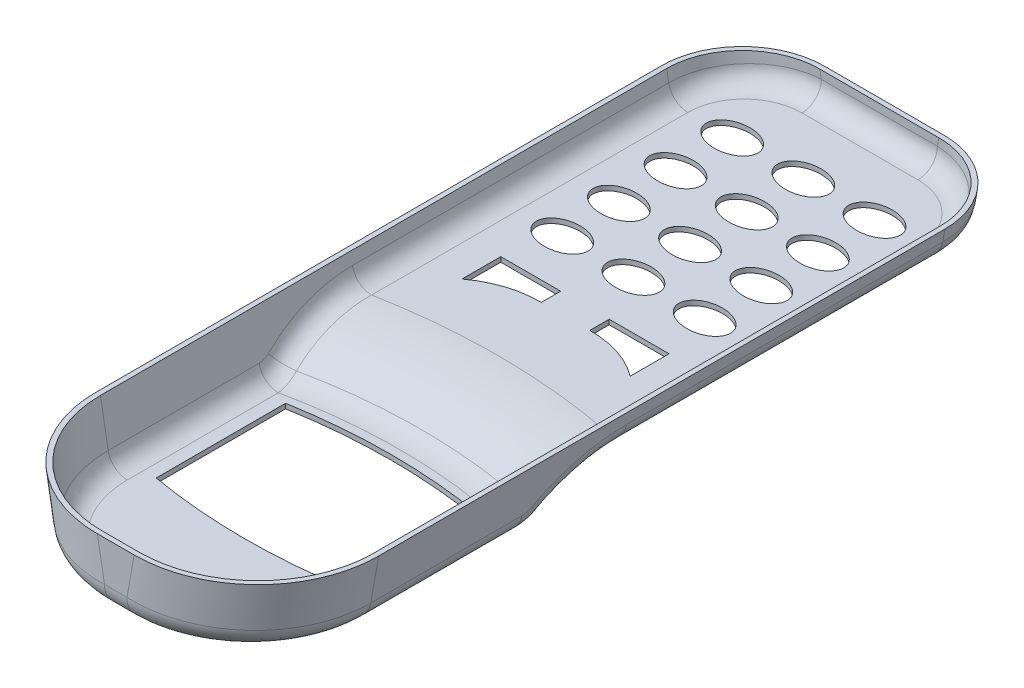
SolidWorks part; units mm, degrees
ref_plane "정면" through (0, 0, 0) normal (0, 0, 1) x (1, 0, 0)
ref_plane "윗면" through (0, 0, 0) normal (0, 1, 0) x (1, 0, 0)
ref_plane "우측면" through (0, 0, 0) normal (1, 0, 0) x (0, 0, -1)
sketch "스케치1" plane through (0, 0, 0) normal (0, 1, 0) x (1, 0, 0)
  line L1 (-8.75, 47.5) -> (8.75, 47.5)
  line L2 (-8.75, 47.5) -> (-8.75, 0)
  line L3 (-8.75, 0) -> (8.75, 0)
  line L4 (8.75, 47.5) -> (8.75, 0)
  dimension "D1" = 17.5
  dimension "D2" = 47.5
extrude "보스-돌출1" add sketch "스케치1" along normal blind 2
sketch "스케치2" plane through (0, 0, 0) normal (0, -1, 0) x (1, 0, 0)
  line L1 (-8.75, 0) -> (8.75, 0)
  line L2 (-8.75, 0) -> (-8.75, -18.8886)
  line L4 (8.75, 0) -> (8.75, -18.8886)
  arc A0 (-8.75, -18.8886) -> (8.75, -18.8886) centre (0, 15) ccw
  point P10 (0, 0)
  dimension "D2" = 35
  dimension "D1" = 18.8886
extrude "보스-돌출2" add sketch "스케치2" along normal blind 2
sketch "스케치3" plane through (0, 0, -47.5) normal (0, 0, -1) x (-1, 0, 0)
  line L0 (-8.75, 2) -> (-8.0447, -2)
  line L2 (-8.0447, -2) -> (-8.75, -2)
  line L3 (-8.75, -2) -> (-8.75, 2)
  line L4 (-8.75, 2) -> (8.75, 2) construction
  line L5 (0, 9.4756) -> (0, -9.7155) construction
  line L6 (8.75, -2) -> (8.75, 2)
  line L7 (8.0447, -2) -> (8.75, -2)
  line L8 (8.75, 2) -> (8.0447, -2)
  line L9 (-8.75, -2) -> (8.75, -2) construction
  point P3 (-7.9664, -2.4442)
  point P15 (0, 0)
  dimension "D1" = 80
extrude "컷-돌출1" cut sketch "스케치3" against normal through all
fillet "필렛1" radius 7.5 2 edges at (8.3973, 0, 0) (-8.3973, 0, 0)
fillet "필렛2" radius 5 2 edges at (8.5737, 1, -47.5) (-8.5737, 1, -47.5)
fillet "필렛3" radius 2.5 1 edges at (0, -2, -20)
fillet "필렛4" radius 7.7 1 edges at (0, 0, -20)
fillet "필렛5" radius 1.5 14 edges at (0, -2, 0) (0, 0, -47.5) (5.8141, -2, -2.1967) (-5.8141, -2, -2.1967) (-8.0447, -2, -12.0204) (-8.3973, 0, -32.5964) (-6.9103, 0, -46.0355) (6.9103, 0, -46.0355) (8.3973, 0, -32.5964) (8.0447, -2, -12.0204) (-8.0795, -1.8026, -17.5361) (8.0689, -1.8624, -17.3781) (-8.3226, -0.4242, -20.1239) (8.3349, -0.3539, -20.3395)
shell "쉘1" thickness 0.3 removed face at (0, 2, -24.2456)
sketch "스케치4" plane through (0, -2, 0) normal (0, -1, 0) x (1, 0, 0)
  line L2 (-6, -8.5) -> (-6, -16.5)
  line L4 (6, -8.5) -> (6, -16.5)
  arc A0 (-6, -8.5) -> (6, -8.5) centre (0, -42.9819) cw
  arc A1 (-6, -16.5) -> (6, -16.5) centre (0, 17.9819) ccw
  point P7 (0, 0)
  point P8 (0, 0)
  point P9 (0, 0)
  point P10 (0, 0)
  point P11 (0, 0)
  dimension "D5" = 35
  dimension "D6" = 35
  dimension "D1" = 8
  dimension "D2" = 12
  dimension "D3" = 8
  dimension "D4" = 6
  dimension "D7" = 8.5
extrude "컷-돌출2" cut sketch "스케치4" against normal through all
sketch "스케치5" plane through (0, 0, 0) normal (0, -1, 0) x (1, 0, 0)
  line L0 (3.5847, -47.5) -> (-3.5847, -47.5) construction
  line L1 (-16.3118, -42.5) -> (22.2927, -42.5) construction
  line L2 (-16.3118, -39) -> (22.2927, -39) construction
  line L3 (-16.3118, -35.5) -> (22.2927, -35.5) construction
  line L4 (-16.3118, -32) -> (22.2927, -32) construction
  line L5 (-5.2, -26.6) -> (-5.2, -29)
  line L6 (-5.2, -29) -> (-1.5, -29)
  line L7 (-1.5, -29) -> (-1.5, -27.8)
  line L8 (0, 0) -> (0, -65.6566) construction
  line L9 (1.5, -29) -> (1.5, -27.8)
  line L10 (5.2, -29) -> (1.5, -29)
  line L11 (5.2, -26.6) -> (5.2, -29)
  arc A0 (-5.2, -26.6) -> (-1.5, -27.8) centre (-1.5989, -21.8008) ccw
  arc A1 (5.2, -26.6) -> (1.5, -27.8) centre (1.5989, -21.8008) cw
  ellipse E0 centre (0, -42.5) end of major axis (-1.6, -42.5) minor radius 1.1
  ellipse E1 centre (4.4, -42.5) end of major axis (6, -42.5) minor radius 1.1
  ellipse E2 centre (-4.4, -42.5) end of major axis (-2.8, -42.5) minor radius 1.1
  ellipse E3 centre (0, -39) end of major axis (-1.6, -39) minor radius 1.1
  ellipse E4 centre (4.4, -39) end of major axis (6, -39) minor radius 1.1
  ellipse E5 centre (-4.4, -39) end of major axis (-2.8, -39) minor radius 1.1
  ellipse E6 centre (0, -35.5) end of major axis (-1.6, -35.5) minor radius 1.1
  ellipse E7 centre (4.4, -35.5) end of major axis (6, -35.5) minor radius 1.1
  ellipse E8 centre (-4.4, -35.5) end of major axis (-2.8, -35.5) minor radius 1.1
  ellipse E9 centre (0, -32) end of major axis (-1.6, -32) minor radius 1.1
  ellipse E10 centre (4.4, -32) end of major axis (2.8, -32) minor radius 1.1
  ellipse E11 centre (-4.4, -32) end of major axis (-6, -32) minor radius 1.1
  point P95 (0, 0)
  point P96 (0, 0)
  dimension "D11" = 6
  dimension "D1" = 2.2
  dimension "D2" = 3.2
  dimension "D3" = 5
  dimension "D4" = 5
  dimension "D5" = 5
  dimension "D6" = 42.5
  dimension "D7" = 4
  dimension "D8" = 1.2
  dimension "D9" = 2.4
  dimension "D10" = 3.7
  dimension "D12" = 1.5
  dimension "D13" = 18.5
extrude "컷-돌출3" cut sketch "스케치5" against normal through all
